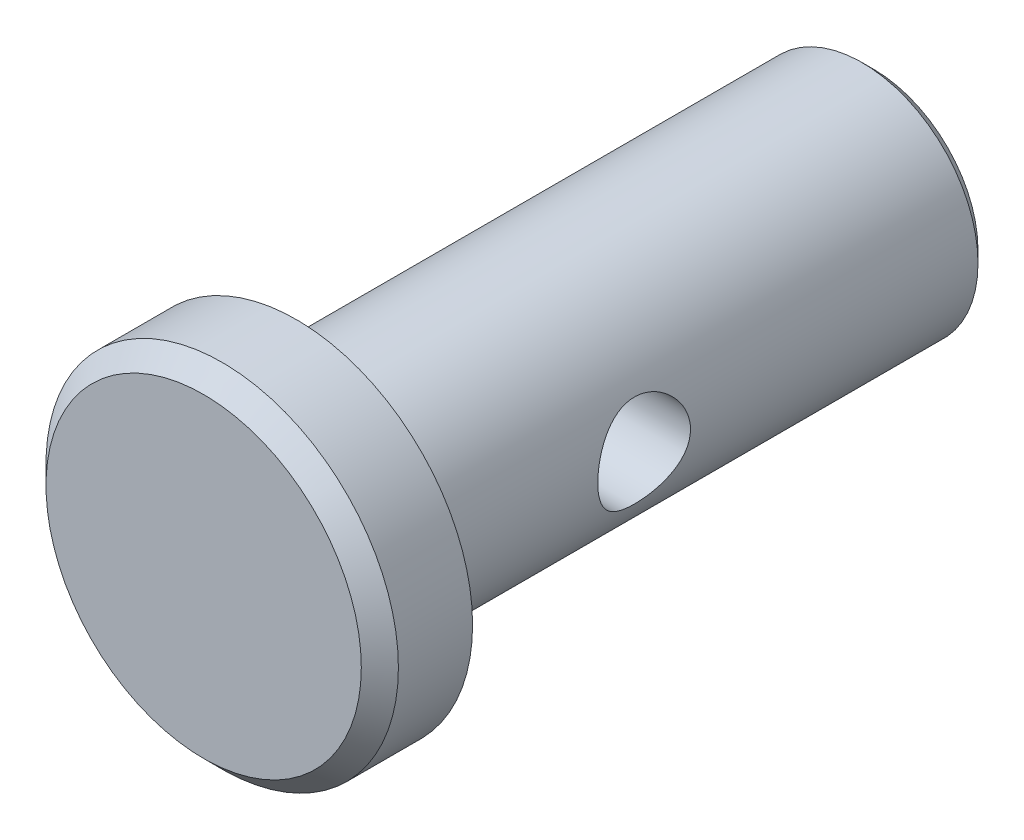
SolidWorks part; units mm, degrees
ref_plane "Front" through (0, 0, 0) normal (0, 0, 1) x (1, 0, 0)
ref_plane "Top" through (0, 0, 0) normal (0, 1, 0) x (1, 0, 0)
ref_plane "Right" through (0, 0, 0) normal (1, 0, 0) x (0, 0, -1)
sketch "Sketch1" plane through (0, 0, 0) normal (0, 0, 1) x (1, 0, 0)
  circle A0 centre (0, 0) radius 3.175
  point P3 (0, 3.175)
  point P4 (0, -3.175)
  dimension "dia" = 6.35
extrude "Extrude1" add sketch "Sketch1" along normal blind 14.2875 and the other way blind 1.524
sketch "Sketch2" plane through (0, 0, 14.2875) normal (0, 0, 1) x (1, 0, 0)
  circle A0 centre (0, 0) radius 4.826
  dimension "head dia" = 9.652
extrude "Extrude2" add sketch "Sketch2" along normal blind 2.54
chamfer "Chamfer1" distance 0.508 angle 45 1 edges at (4.826, 0, 16.8275)
sketch "Sketch3" plane through (0, 0, 0) normal (1, 0, 0) x (0, 0, -1)
  line L0 (-14.2875, -3.175) -> (-14.2875, 3.175) construction
  circle A0 centre (-0.2921, 0) radius 0.9144
  point P2 (-1.2065, 0)
  dimension "hole dia" = 1.8288
  dimension "useable Lg" = 13.081
chamfer "Chamfer2" distance 0.3175 angle 45 1 edges at (3.175, 0, -1.524)
ref_plane "Plane1" through (0, 0, 0.2921) normal (0, 0, 1) x (1, 0, 0)
sketch "Sketch8" plane through (0, 0, 0) normal (1, 0, 0) x (0, 0, -1)
  line L0 (-16.8275, 4.318) -> (-16.8275, -4.318) construction
  line L1 (-16.3195, -4.826) -> (-14.2875, -4.826) construction
  line L2 (1.524, -2.8575) -> (1.524, 2.8575) construction
  point P0 (-16.8275, 4.826)
  point P1 (-14.2875, 4.826)
  point P5 (1.524, 3.175)
  point P8 (-16.8275, -4.826)
  point P9 (1.524, -3.175)
sketch "Sketch9" plane through (0, 0, 0) normal (1, 0, 0) x (0, 0, -1)
  line L0 (-14.2875, -3.175) -> (-14.2875, 3.175) construction
  circle A0 centre (-7.9375, 0) radius 1.27
  dimension "D1" = 2.54
  dimension "D2" = 6.35
extrude "Cut-Extrude1" cut sketch "Sketch9" against normal blind 3.175 and the other way blind 3.175
equation "\"D1@Chamfer1\" = \"head ht@Extrude2\" * .2"
equation "\"D1@Chamfer2\" = \"dia@Sketch1\" * .05"
